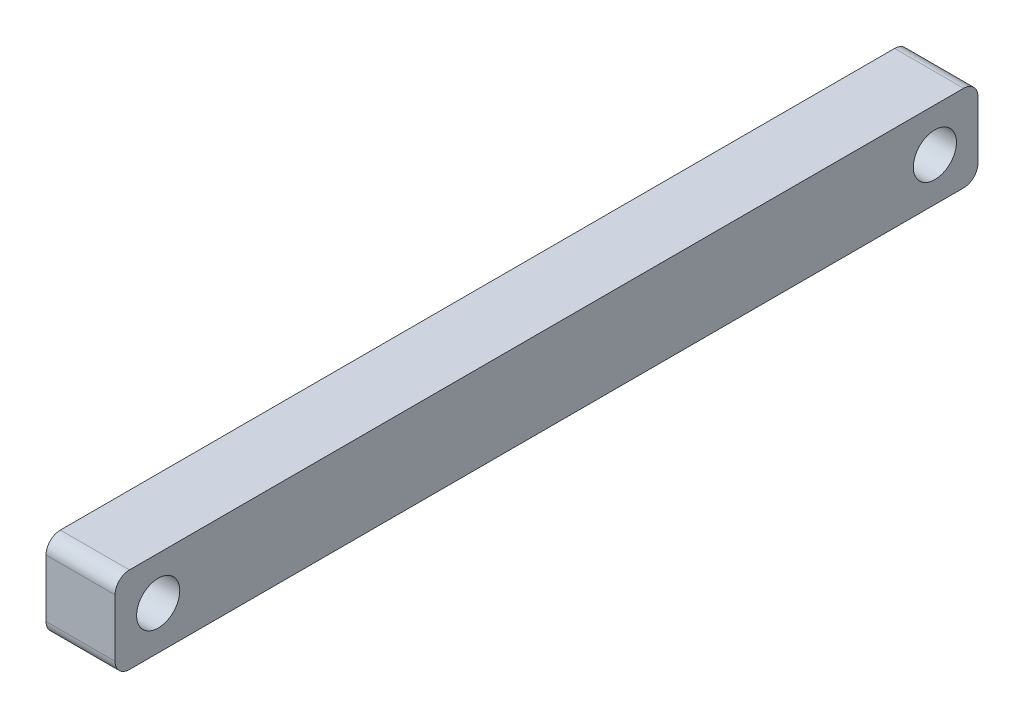
SolidWorks part; units mm, degrees
ref_plane "Alzado" through (0, 0, 0) normal (0, 0, 1) x (1, 0, 0)
ref_plane "Planta" through (0, 0, 0) normal (0, 1, 0) x (1, 0, 0)
ref_plane "Vista lateral" through (0, 0, 0) normal (1, 0, 0) x (0, 0, -1)
sketch "Croquis1" plane through (0, 0, 0) normal (1, 0, 0) x (0, 0, -1)
  line L0 (-29, 3) -> (29, 3)
  line L2 (-30, 0) -> (30, 0) construction
  line L3 (-30, 2) -> (-30, -2)
  line L4 (-29, -3) -> (29, -3)
  line L5 (30, 2) -> (30, -2)
  arc A0 (-30, -2) -> (-29, -3) centre (-29, -2) ccw
  arc A1 (-30, 2) -> (-29, 3) centre (-29, 2) cw
  arc A2 (29, -3) -> (30, -2) centre (29, -2) ccw
  arc A3 (29, 3) -> (30, 2) centre (29, 2) cw
  point P1 (0, 0)
  point P9 (-30, -3)
  point P13 (-30, 3)
  point P16 (30, -3)
  point P19 (30, 3)
  dimension "D3" = 1
  dimension "D4" = 1
  dimension "D1" = 3
  dimension "D2" = 60
extrude "Saliente-Extruir1" add sketch "Croquis1" along normal mid plane 4.8
sketch "Croquis2" plane through (0, 0, 0) normal (1, 0, 0) x (0, 0, -1)
  line L0 (-30, 2) -> (-30, -2) construction
  line L1 (30, -2) -> (30, 2) construction
  circle A0 centre (-27, 0) radius 1.5
  circle A1 centre (27, 0) radius 1.5
  dimension "D1" = 3
  dimension "D3" = 3
  dimension "D2" = 3
  dimension "D4" = 3
extrude "Cortar-Extruir1" cut sketch "Croquis2" against normal through all both and the other way through all
